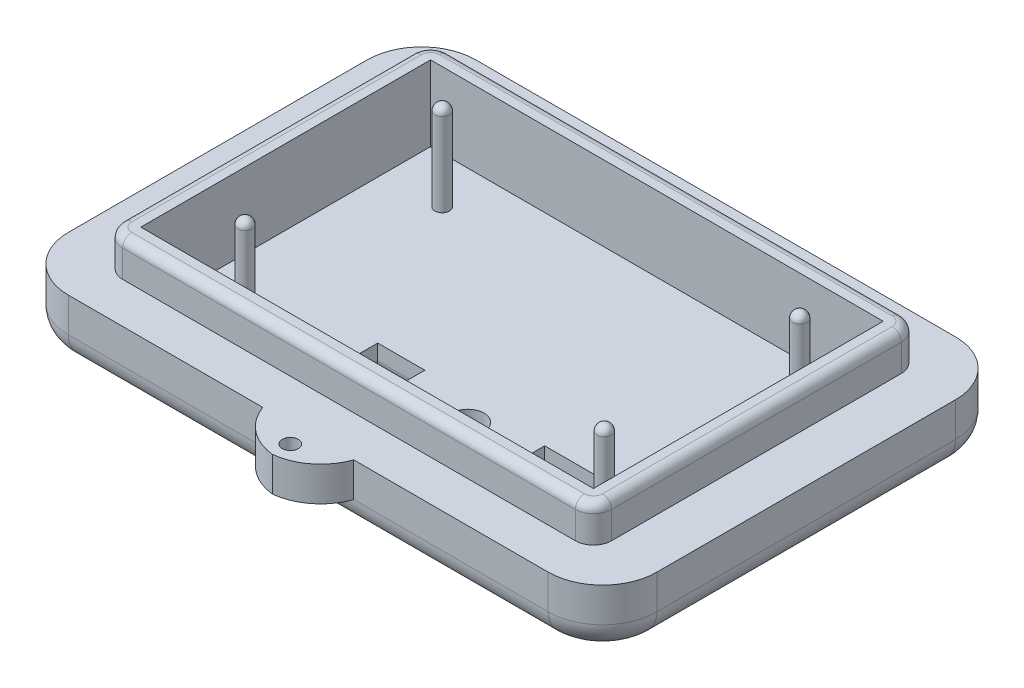
SolidWorks part; units mm, degrees
ref_plane "Front Plane" through (0, 0, 0) normal (0, 0, 1) x (1, 0, 0)
ref_plane "Top Plane" through (0, 0, 0) normal (0, 1, 0) x (1, 0, 0)
ref_plane "Right Plane" through (0, 0, 0) normal (1, 0, 0) x (0, 0, -1)
sketch "Sketch1" plane through (0, 0, 0) normal (0, 1, 0) x (1, 0, 0)
  line L1 (0, 0) -> (82.55, 0)
  line L2 (0, 0) -> (0, 57.15)
  line L3 (0, 57.15) -> (82.55, 57.15)
  line L4 (82.55, 0) -> (82.55, 57.15)
  dimension "D1" = 57.15
  dimension "D2" = 82.55
extrude "Boss-Extrude1" add sketch "Sketch1" along normal blind 8.636
fillet "Fillet2" radius 7.62 4 edges at (82.55, 4.318, -57.15) (82.55, 4.318, 0) (0, 4.318, 0) (0, 4.318, -57.15)
fillet "Fillet3" radius 3.81 8 edges at (80.3182, 0, -54.9182) (82.55, 0, -28.575) (80.3182, 0, -2.2318) (41.275, 0, 0) (2.2318, 0, -2.2318) (0, 0, -28.575) (2.2318, 0, -54.9182) (41.275, 0, -57.15)
sketch "Sketch2" plane through (0, 8.636, 0) normal (0, 1, 0) x (1, 0, 0)
  line L0 (0, 28.575) -> (82.55, 28.575) construction
  line L1 (0, 49.53) -> (0, 7.62) construction
  line L2 (82.55, 7.62) -> (82.55, 49.53) construction
  line L4 (9.525, 8.255) -> (73.025, 8.255)
  line L5 (9.525, 8.255) -> (9.525, 48.895)
  line L6 (9.525, 48.895) -> (73.025, 48.895)
  line L7 (73.025, 8.255) -> (73.025, 48.895)
  line L8 (9.525, 8.255) -> (73.025, 48.895) construction
  line L9 (9.525, 48.895) -> (73.025, 8.255) construction
  point P6 (41.275, 28.575)
  dimension "D1" = 40.64
  dimension "D2" = 63.5
extrude "Cut-Extrude1" cut sketch "Sketch2" against normal blind 5.461
sketch "Sketch7" plane through (0, 8.636, 0) normal (0, 1, 0) x (1, 0, 0)
  line L14 (6.985, 51.435) -> (6.985, 5.715)
  line L15 (6.985, 5.715) -> (75.565, 5.715)
  line L16 (75.565, 5.715) -> (75.565, 51.435)
  line L17 (75.565, 51.435) -> (6.985, 51.435)
  line L18 (6.985, 51.435) -> (6.985, 5.715)
  line L19 (6.985, 5.715) -> (75.565, 5.715)
  line L20 (75.565, 5.715) -> (75.565, 51.435)
  line L21 (75.565, 51.435) -> (6.985, 51.435)
  dimension "D1" = 2.54
extrude "Boss-Extrude3" add sketch "Sketch7" along normal blind 5.08
sketch "Sketch8" plane through (0, 13.716, 0) normal (0, 1, 0) x (1, 0, 0)
  line L8 (73.025, 48.895) -> (9.525, 48.895)
  line L9 (9.525, 48.895) -> (9.525, 8.255)
  line L10 (9.525, 8.255) -> (73.025, 8.255)
  line L11 (73.025, 8.255) -> (73.025, 48.895)
  line L12 (73.025, 48.895) -> (9.525, 48.895)
  line L13 (9.525, 48.895) -> (9.525, 8.255)
  line L14 (9.525, 8.255) -> (73.025, 8.255)
  line L15 (73.025, 8.255) -> (73.025, 48.895)
  dimension "D1" = 2.54
extrude "Cut-Extrude3" cut sketch "Sketch8" against normal blind 5.08
sketch "Sketch5" plane through (0, 3.175, 0) normal (0, 1, 0) x (1, 0, 0)
  line L3 (9.525, 8.255) -> (73.025, 8.255) construction
  line L4 (73.025, 8.255) -> (73.025, 48.895) construction
  circle A0 centre (17.665, 42.392) radius 1.016
  circle A1 centre (17.665, 14.732) radius 1.016
  circle A2 centre (67.945, 42.259) radius 1.016
  circle A3 centre (67.945, 14.859) radius 1.016
  point P2 (0, 0)
  point P3 (0, 0)
  dimension "D5" = 2.032
  dimension "D6" = 2.032
  dimension "D7" = 2.032
  dimension "D8" = 2.032
  dimension "D11" = 6.604
  dimension "D2" = 27.66
  dimension "D3" = 6.477
  dimension "D4" = 50.28
  dimension "D9" = 27.4
  dimension "D10" = 5.08
  dimension "D12" = 5.08
  dimension "D13" = 50.28
extrude "Boss-Extrude4" add sketch "Sketch5" along normal blind 12.7
sketch "Sketch4" plane through (0, 3.175, 0) normal (0, 1, 0) x (1, 0, 0)
  line L4 (66.471, 20.559) -> (53.871, 20.559)
  line L5 (66.471, 20.559) -> (66.471, 15.559)
  line L6 (66.471, 15.559) -> (53.871, 15.559)
  line L7 (53.871, 20.559) -> (53.871, 15.559)
  line L8 (66.471, 20.559) -> (53.871, 15.559) construction
  line L9 (66.471, 15.559) -> (53.871, 20.559) construction
  line L11 (36.285, 21.336) -> (29.681, 21.336)
  line L12 (36.285, 21.336) -> (36.285, 14.732)
  line L13 (36.285, 14.732) -> (29.681, 14.732)
  line L14 (29.681, 21.336) -> (29.681, 14.732)
  line L15 (36.285, 21.336) -> (29.681, 14.732) construction
  line L16 (36.285, 14.732) -> (29.681, 21.336) construction
  circle A0 centre (45.641, 18.034) radius 2.25
  circle A1 centre (17.665, 14.732) radius 1.016 construction
  circle A2 centre (67.945, 14.859) radius 1.016 construction
  point P7 (60.171, 18.059)
  point P15 (32.983, 18.034)
  dimension "D3" = 4.5
  dimension "D4" = 5.7
  dimension "D2" = 15.96
  dimension "D5" = 12.6
  dimension "D6" = 5
  dimension "D7" = 20.83
  dimension "D8" = 6.604
  dimension "D9" = 6.604
  dimension "D10" = 0
  dimension "D11" = 18.62
  dimension "D13" = 0
extrude "Cut-Extrude2" cut sketch "Sketch4" against normal blind 7.366
fillet "Fillet7" radius 1.016 3 edges at (17.665, 15.875, -13.716) (17.665, 15.875, -41.376) (67.945, 15.875, -41.243)
fillet "Fillet8" radius 2.54 4 edges at (75.565, 11.176, -51.435) (75.565, 11.176, -5.715) (6.985, 11.176, -5.715) (6.985, 11.176, -51.435)
sketch "Sketch9" plane through (0, 0, 0) normal (0, 0, 1) x (1, 0, 0)
  line L0 (41.275, 8.636) -> (41.275, 3.81) construction
  line L1 (7.62, 8.636) -> (74.93, 8.636) construction
  line L2 (7.62, 3.81) -> (74.93, 3.81) construction
  line L4 (47.6519, 8.636) -> (34.8981, 8.636)
  line L5 (47.6519, 8.636) -> (47.6519, 3.81)
  line L6 (47.6519, 3.81) -> (34.8981, 3.81)
  line L7 (34.8981, 8.636) -> (34.8981, 3.81)
  line L8 (47.6519, 8.636) -> (34.8981, 3.81) construction
  line L9 (47.6519, 3.81) -> (34.8981, 8.636) construction
  point P6 (41.275, 6.223)
extrude "Boss-Extrude5" add sketch "Sketch9" along normal blind 5.08
fillet "Fillet10" radius 7.62 2 edges at (47.6519, 6.223, 5.08) (34.8981, 6.223, 5.08)
fillet "Fillet11" radius 1.27 8 edges at (74.8211, 13.716, -50.6911) (75.565, 13.716, -28.575) (74.8211, 13.716, -6.4589) (41.275, 13.716, -5.715) (7.7289, 13.716, -6.4589) (7.7289, 13.716, -50.6911) (6.985, 13.716, -28.575) (41.275, 13.716, -51.435)
fillet "Fillet12" radius 1.016 1 edges at (67.945, 15.875, -13.843)
sketch "Sketch17" plane through (0, 3.81, 0) normal (0, -1, 0) x (1, 0, 0)
  line L0 (41.275, 5.0371) -> (41.275, 0) construction
  point P3 (41.275, 2.5186)
hole_wizard "#4-40 Tapped Hole2" positions "Sketch18" profile "Sketch19" tap size "#4-40" standard "ANSI Inch"
sketch "Sketch18" plane through (0, 3.81, 0) normal (0, -1, 0) x (-1, 0, 0)
  point P0 (-41.275, -2.5186)
sketch "Sketch19" plane through (41.275, 3.81, 2.5186) normal (1, 0, 0) x (0, 0, -1)
  line L0 (0, 0) -> (0, 8.2992)
  line L1 (0, 8.2992) -> (1.1303, 7.62)
  line L2 (1.1303, 7.62) -> (1.1303, 0.7779)
  line L3 (1.1303, 0.7779) -> (2.0574, 0)
  line L5 (2.0574, 0) -> (0, 0)
  line L6 (-1.1303, 0.7779) -> (-2.0574, 0) construction
  line L10 (0, 8.2992) -> (-1.1303, 7.62) construction
  line L11 (0, -6.35) -> (0, 107.95) construction
  dimension "Tap Drill Dia." = 2.2606
  dimension "Tap Drill Depth" = 7.62
  dimension "Near C'Sink Dia." = 4.1148
  dimension "Near C'Sink Angle" = 100
  dimension "Drill Angle" = 118
cosmetic thread "Hole Thread2" parameters "D1"=4.826, "D2"=2.8448
fillet "Fillet13" radius 1.016 9 edges at (66.471, 0, -18.059) (60.171, 0, -15.559) (53.871, 0, -18.059) (60.171, 0, -20.559) (45.641, 0, -20.284) (29.681, 0, -18.034) (32.983, 0, -14.732) (36.285, 0, -18.034) (32.983, 0, -21.336)
